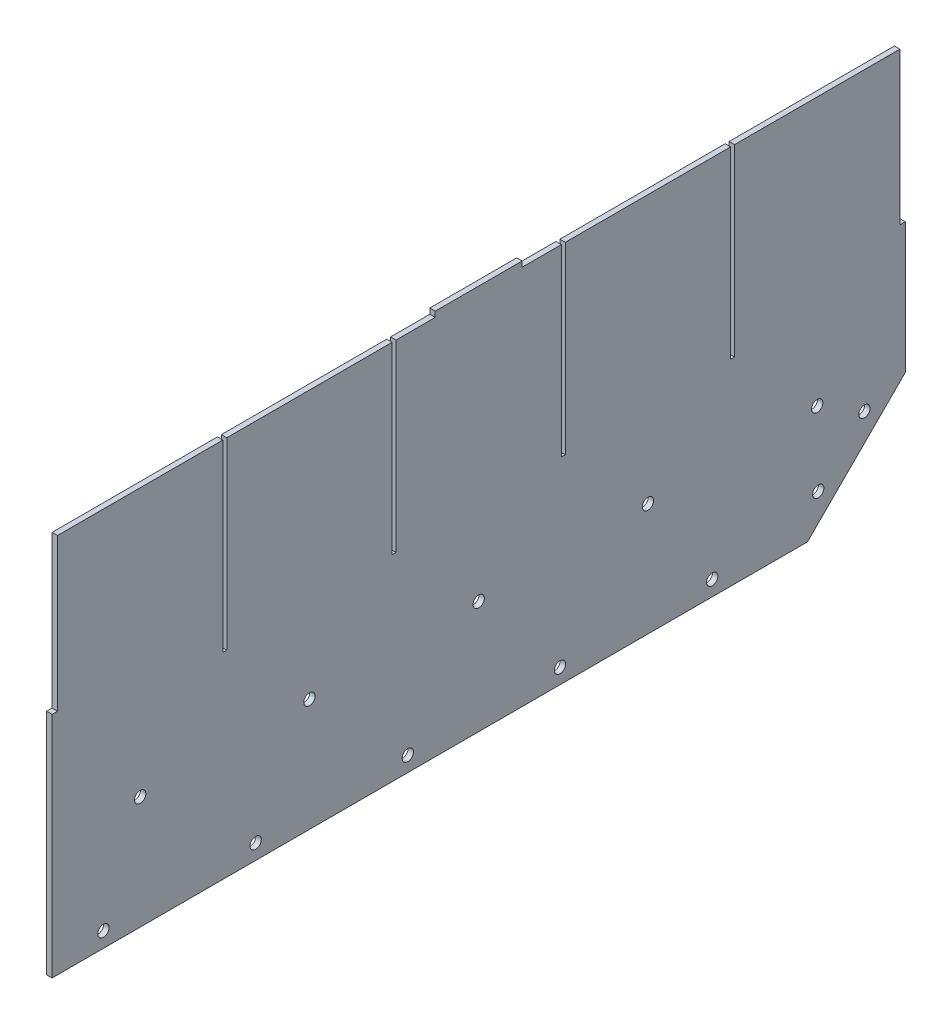
SolidWorks part; units mm, degrees
material "6061-T6 (SS)"
ref_plane "X-Y Datum" through (0, 0, 0) normal (0, 0, 1) x (1, 0, 0)
ref_plane "X-Z Datum" through (0, 0, 0) normal (0, 1, 0) x (1, 0, 0)
ref_plane "Y-Z Datum" through (0, 0, 0) normal (1, 0, 0) x (0, 0, -1)
sketch "Sketch1" plane through (0, 0, 0) normal (1, 0, 0) x (0, 0, -1)
  line L1 (-249.174, 82.55) -> (249.174, 82.55)
  line L2 (-249.174, 82.55) -> (-249.174, -82.55)
  line L3 (-249.174, -82.55) -> (249.174, -82.55)
  line L4 (249.174, 82.55) -> (249.174, -82.55)
  line L5 (-249.174, 82.55) -> (249.174, -82.55) construction
  line L6 (-249.174, -82.55) -> (249.174, 82.55) construction
  point P0 (0, 0)
  dimension "D1" = 165.1
  dimension "D2" = 498.348
extrude "Boss-Extrude1" add sketch "Sketch1" along normal mid plane 3.175
sketch "Sketch2" plane through (1.5875, 0, 0) normal (1, 0, 0) x (0, 0, -1)
  line L3 (192.024, -139.7) -> (-249.174, -139.7)
  line L5 (-249.174, -82.55) -> (249.174, -82.55) construction
  line L6 (-249.174, -82.55) -> (249.174, -82.55)
  line L7 (-249.174, -82.55) -> (-249.174, -139.7)
  line L12 (192.024, -139.7) -> (249.174, -82.55)
  line M10 (-249.174, -82.55) -> (249.174, -82.55)
  dimension "D1" = 45
  dimension "D5" = 57.15
extrude "Boss-Extrude2" add sketch "Sketch2" against normal blind 3.175 contours L3 L12 M10 region at (1.5875, -110.5456, 13.9978)
sketch "Sketch3" plane through (1.5875, 0, 0) normal (1, 0, 0) x (0, 0, -1)
  line L0 (-219.202, -139.7) -> (-219.202, -130.81)
  line L1 (192.024, -139.7) -> (-249.174, -139.7) construction
  line L2 (-219.202, -130.81) -> (-249.174, -130.81)
  line L3 (-249.174, 82.55) -> (-249.174, -139.7) construction
  circle A0 centre (-219.202, -130.81) radius 3.302
  dimension "D1" = 29.972
  dimension "D3" = 6.604
  dimension "D2" = 8.89
extrude "Cut-Extrude1" cut sketch "Sketch3" against normal blind 3.175 contours L2 A0 L0 | L0 A0 L2 region at (1.5875, -132.2114, 220.6034) region at (1.5875, -130.3429, 218.7349)
pattern_linear "LPattern1" count 5 spacing 88.9 along (0, 0, -1) of "Cut-Extrude1"
sketch "Sketch4" plane through (1.5875, 0, 0) normal (1, 0, 0) x (0, 0, -1)
  line L0 (192.024, -139.7) -> (183.9418, -131.6178)
  line L1 (183.9418, -131.6178) -> (198.3102, -117.2494)
  circle A0 centre (198.3102, -117.2494) radius 3.302
  dimension "D1" = 6.604
extrude "Cut-Extrude2" cut sketch "Sketch4" against normal through all contours A0 region at (1.5875, -120.2137, -199.5381)
pattern_linear "LPattern2" count 2 spacing 38.1 along (0, 0.7071, -0.7071) of "Cut-Extrude2"
sketch "Sketch5" plane through (-1.5875, 0, 0) normal (-1, 0, 0) x (0, 0, 1)
  line L0 (245.872, 82.677) -> (245.872, -6.477)
  line L1 (-249.174, 82.55) -> (-245.999, 82.55)
  line L2 (-249.174, 82.55) -> (-249.174, -6.35)
  line L3 (-249.174, -6.35) -> (-245.999, -6.35)
  line L4 (-245.999, 82.55) -> (-245.999, -6.35)
  line L5 (249.174, 82.55) -> (245.999, 82.55)
  line L6 (249.174, 82.55) -> (249.174, -6.35)
  line L7 (249.174, -6.35) -> (245.999, -6.35)
  line L8 (245.999, 82.55) -> (245.999, -6.35)
  line L9 (249.301, -6.477) -> (245.872, -6.477)
  line L10 (249.301, 82.677) -> (249.301, -6.477)
  line L11 (249.301, 82.677) -> (245.872, 82.677)
  line L12 (-245.872, 82.677) -> (-245.872, -6.477)
  line L13 (-249.301, -6.477) -> (-245.872, -6.477)
  line L14 (-249.301, 82.677) -> (-249.301, -6.477)
  line L15 (-249.301, 82.677) -> (-245.872, 82.677)
  line M9 (-249.174, 82.55) -> (-249.174, -82.55)
  line M12 (249.174, -139.7) -> (249.174, 82.55)
  line M13 (249.174, 82.55) -> (-249.174, 82.55)
  dimension "D1" = 3.175
  dimension "D2" = 88.9
  dimension "D3" = 3.175
  dimension "D4" = 88.9
  dimension "D5" = 0.127
extrude "Cut-Extrude3" cut sketch "Sketch5" against normal through all contours L4 L3 M13 M9 | L8 L7 M13 M12 region at (-1.5875, 38.1, 247.5865) region at (-1.5875, 38.1, -247.5865)
sketch "Sketch6" plane through (-1.5875, 0, 0) normal (-1, 0, 0) x (0, 0, 1)
  line L0 (-149.5933, 82.7151) -> (-146.9771, 82.7151)
  line L1 (-149.4282, 82.55) -> (-149.4282, -24.892) construction
  line L2 (-122.174, 82.55) -> (-249.174, 82.55)
  line L3 (-149.4282, 82.55) -> (-149.4282, -24.892)
  line L4 (-146.9771, 82.7151) -> (-146.9771, -25.0571)
  line L5 (-149.4282, 82.55) -> (-147.1422, 82.55)
  line L6 (-149.4282, 82.55) -> (-149.4282, -24.892)
  line L7 (-149.4282, -24.892) -> (-147.1422, -24.892)
  line L8 (-147.1422, 82.55) -> (-147.1422, -24.892)
  line L9 (-149.5933, -25.0571) -> (-146.9771, -25.0571)
  line L10 (-149.5933, 82.7151) -> (-149.5933, -25.0571)
  line M9 (245.999, 82.55) -> (-245.999, 82.55)
  dimension "D1" = 2.286
  dimension "D2" = 107.442
  dimension "D3" = 0.1651
extrude "Cut-Extrude4" cut sketch "Sketch6" against normal through all contours L8 L3 L7 M9 region at (-1.5875, 28.829, -148.2852)
pattern_linear "LPattern3" count 4 spacing 98.8568 along (0, 0, 1) of "Cut-Extrude4"
sketch "Sketch7" plane through (-1.5875, 0, 0) normal (-1, 0, 0) x (0, 0, 1)
  line L0 (122.174, 85.725) -> (25.4, 85.725) construction
  line L1 (25.4, 82.55) -> (-25.4, 82.55)
  line L2 (25.4, 82.55) -> (25.4, 85.725)
  line L3 (25.4, 85.725) -> (-25.4, 85.725)
  line L4 (-25.4, 82.55) -> (-25.4, 85.725)
  line L5 (25.4, 82.55) -> (-25.4, 85.725) construction
  line L6 (25.4, 85.725) -> (-25.4, 82.55) construction
  point P0 (0, 84.1375)
  dimension "D1" = 3.175
  dimension "D2" = 50.8
extrude "Boss-Extrude3" add sketch "Sketch7" against normal blind 3.175
sketch "Sketch8" plane through (1.5875, 0, 0) normal (1, 0, 0) x (0, 0, -1)
  line L0 (192.024, -139.7) -> (-249.174, -139.7) construction
  circle A0 centre (0, -73.8124) radius 3
  dimension "D1" = 6
  dimension "D2" = 65.8876
hole_wizard "M6 Clearance Hole1" positions "Sketch9" profile "Sketch10" hole size "M6" standard "ANSI Metric" end condition through all
sketch "Sketch9" plane through (1.5875, 0, 0) normal (1, 0, 0) x (0, 0, -1)
  point P0 (0, -73.8124)
sketch "Sketch10" plane through (1.5875, -73.8124, 0) normal (0, 1, 0) x (0, 0, -1)
  line L0 (0, 0) -> (0, 3.175)
  line L1 (0, 3.175) -> (3.3, 3.175)
  line L2 (3.3, 3.175) -> (3.3, 0)
  line L5 (3.3, 0) -> (0, 0)
  line L11 (0, -6.35) -> (0, 107.95) construction
  dimension "Thru Hole Dia." = 6.6
  dimension "Thru Hole Depth" = 3.175
pattern_linear "LPattern4" count 3 spacing 98.8568 along (0, 0, 1) count 3 spacing 98.8568 along (0, 0, -1) of "M6 Clearance Hole1"
